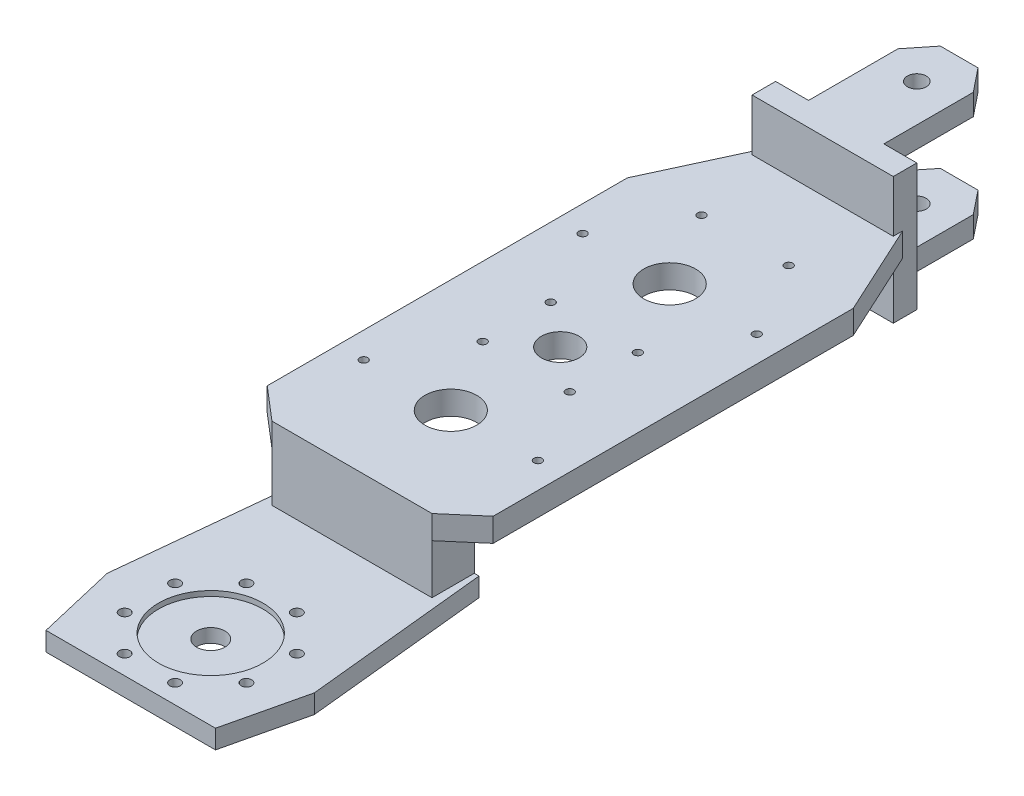
SolidWorks part; units mm, degrees
ref_plane "Front Plane" through (0, 0, 0) normal (0, 0, 1) x (1, 0, 0)
ref_plane "Top Plane" through (0, 0, 0) normal (0, 1, 0) x (1, 0, 0)
ref_plane "Right Plane" through (0, 0, 0) normal (1, 0, 0) x (0, 0, -1)
ref_plane "PL_Knee_Plate_base" through (0, -34, 0) normal (0, 1, 0) x (1, 0, 0)
sketch "SK_Knee_Plate" plane through (0, -34, 0) normal (0, 1, 0) x (1, 0, 0)
  line L0 (-36, -34) -> (36, -34)
  line L1 (36, -34) -> (44, 0)
  line L2 (44, 0) -> (36, 78)
  line L3 (36, 78) -> (-36, 78)
  line L4 (-36, 78) -> (-44, 0)
  line L5 (-44, 0) -> (-36, -34)
  circle A0 centre (25.8686, 10.7151) radius 2.25
  circle A1 centre (10.7151, 25.8686) radius 2.25
  circle A2 centre (-10.7151, 25.8686) radius 2.25
  circle A3 centre (-25.8686, 10.7151) radius 2.25
  circle A4 centre (-25.8686, -10.7151) radius 2.25
  circle A5 centre (-10.7151, -25.8686) radius 2.25
  circle A6 centre (10.7151, -25.8686) radius 2.25
  circle A7 centre (25.8686, -10.7151) radius 2.25
  circle A8 centre (0, 0) radius 6
  dimension "D11_SK_Knee_Plate" = 4.5
  dimension "D14_SK_Knee_Plate" = 4.5
  dimension "D17_SK_Knee_Plate" = 4.5
  dimension "D20_SK_Knee_Plate" = 4.5
  dimension "D23_SK_Knee_Plate" = 4.5
  dimension "D26_SK_Knee_Plate" = 4.5
  dimension "D29_SK_Knee_Plate" = 4.5
  dimension "D32_SK_Knee_Plate" = 4.5
  dimension "D35_SK_Knee_Plate" = 12
  dimension "P1" = 36
  dimension "P2" = 34
  dimension "P3" = 36
  dimension "P4" = 34
  dimension "P5" = 44
  dimension "P6" = 36
  dimension "P7" = 78
  dimension "P8" = 36
  dimension "P9" = 78
  dimension "P10" = 44
  dimension "P12" = 25.8686
  dimension "P13" = 10.7151
  dimension "P15" = 10.7151
  dimension "P16" = 25.8686
  dimension "P18" = 10.7151
  dimension "P19" = 25.8686
  dimension "P21" = 25.8686
  dimension "P22" = 10.7151
  dimension "P24" = 25.8686
  dimension "P25" = 10.7151
  dimension "P27" = 10.7151
  dimension "P28" = 25.8686
  dimension "P30" = 10.7151
  dimension "P31" = 25.8686
  dimension "P33" = 25.8686
  dimension "P34" = 10.7151
extrude "Knee_Plate" add sketch "SK_Knee_Plate" along normal blind 8
ref_plane "PL_Knee_Pilot_Recess_base" through (0, -26, 0) normal (0, 1, 0) x (1, 0, 0)
sketch "SK_Knee_Pilot_Recess" plane through (0, -26, 0) normal (0, 1, 0) x (1, 0, 0)
  circle A0 centre (0, 0) radius 22.15
  dimension "D1_SK_Knee_Pilot_Recess" = 44.3
extrude "Knee_Pilot_Recess" cut sketch "SK_Knee_Pilot_Recess" against normal blind 2.2
ref_plane "PL_Joggle_base" through (0, 0, -78) normal (0, 0, 1) x (1, 0, 0)
sketch "SK_Joggle" plane through (0, 0, -78) normal (0, 0, 1) x (1, 0, 0)
  line L0 (-34, -34) -> (34, -34)
  line L1 (34, -34) -> (34, 5)
  line L2 (34, 5) -> (-34, 5)
  line L3 (-34, 5) -> (-34, -34)
  dimension "P1" = 34
  dimension "P2" = 34
  dimension "P3" = 34
  dimension "P4" = 34
  dimension "P5" = 34
  dimension "P6" = 5
  dimension "P7" = 34
  dimension "P8" = 5
extrude "Joggle" add sketch "SK_Joggle" along normal blind 18
ref_plane "PL_Web_base" through (0, -5, 0) normal (0, 1, 0) x (1, 0, 0)
sketch "SK_Web" plane through (0, -5, 0) normal (0, 1, 0) x (1, 0, 0)
  line L0 (-34, 60) -> (34, 60)
  line L1 (34, 60) -> (48, 72)
  line L2 (48, 72) -> (48, 225)
  line L3 (48, 225) -> (30, 264)
  line L4 (30, 264) -> (-30, 264)
  line L5 (-30, 264) -> (-48, 225)
  line L6 (-48, 225) -> (-48, 72)
  line L7 (-48, 72) -> (-34, 60)
  circle A0 centre (37, 102) radius 1.7
  circle A1 centre (18.5, 134.0429) radius 1.7
  circle A2 centre (-18.5, 134.0429) radius 1.7
  circle A3 centre (-37, 102) radius 1.7
  circle A4 centre (-18.5, 69.9571) radius 1.7
  circle A5 centre (18.5, 69.9571) radius 1.7
  circle A6 centre (37, 195) radius 1.7
  circle A7 centre (18.5, 227.0429) radius 1.7
  circle A8 centre (-18.5, 227.0429) radius 1.7
  circle A9 centre (-37, 195) radius 1.7
  circle A10 centre (-18.5, 162.9571) radius 1.7
  circle A11 centre (18.5, 162.9571) radius 1.7
  circle A12 centre (0, 102) radius 11
  circle A13 centre (0, 195) radius 11
  circle A14 centre (0, 148.5) radius 8
  dimension "D17_SK_Web" = 3.4
  dimension "D20_SK_Web" = 3.4
  dimension "D23_SK_Web" = 3.4
  dimension "D26_SK_Web" = 3.4
  dimension "D29_SK_Web" = 3.4
  dimension "D32_SK_Web" = 3.4
  dimension "D35_SK_Web" = 3.4
  dimension "D38_SK_Web" = 3.4
  dimension "D41_SK_Web" = 3.4
  dimension "D44_SK_Web" = 3.4
  dimension "D47_SK_Web" = 3.4
  dimension "D50_SK_Web" = 3.4
  dimension "D53_SK_Web" = 22
  dimension "D55_SK_Web" = 22
  dimension "D57_SK_Web" = 16
  dimension "P1" = 34
  dimension "P2" = 60
  dimension "P3" = 34
  dimension "P4" = 60
  dimension "P5" = 48
  dimension "P6" = 72
  dimension "P7" = 48
  dimension "P8" = 225
  dimension "P9" = 30
  dimension "P10" = 264
  dimension "P11" = 30
  dimension "P12" = 264
  dimension "P13" = 48
  dimension "P14" = 225
  dimension "P15" = 48
  dimension "P16" = 72
  dimension "P18" = 37
  dimension "P19" = 102
  dimension "P21" = 18.5
  dimension "P22" = 134.0429
  dimension "P24" = 18.5
  dimension "P25" = 134.0429
  dimension "P27" = 37
  dimension "P28" = 102
  dimension "P30" = 18.5
  dimension "P31" = 69.9571
  dimension "P33" = 18.5
  dimension "P34" = 69.9571
  dimension "P36" = 37
  dimension "P37" = 195
  dimension "P39" = 18.5
  dimension "P40" = 227.0429
  dimension "P42" = 18.5
  dimension "P43" = 227.0429
  dimension "P45" = 37
  dimension "P46" = 195
  dimension "P48" = 18.5
  dimension "P49" = 162.9571
  dimension "P51" = 18.5
  dimension "P52" = 162.9571
  dimension "P54" = 102
  dimension "P56" = 195
  dimension "P58" = 148.5
extrude "Web" add sketch "SK_Web" along normal blind 10
ref_plane "PL_Fork_Bar_base" through (0, 0, -270) normal (0, 0, 1) x (1, 0, 0)
sketch "SK_Fork_Bar" plane through (0, 0, -270) normal (0, 0, 1) x (1, 0, 0)
  line L0 (-30, -27) -> (30, -27)
  line L1 (30, -27) -> (30, 27)
  line L2 (30, 27) -> (-30, 27)
  line L3 (-30, 27) -> (-30, -27)
  dimension "P1" = 30
  dimension "P2" = 27
  dimension "P3" = 30
  dimension "P4" = 27
  dimension "P5" = 30
  dimension "P6" = 27
  dimension "P7" = 30
  dimension "P8" = 27
extrude "Fork_Bar" add sketch "SK_Fork_Bar" along normal blind 10
ref_plane "PL_Tine_Lat_base" through (0, 18, 0) normal (0, 1, 0) x (1, 0, 0)
sketch "SK_Tine_Lat" plane through (0, 18, 0) normal (0, 1, 0) x (1, 0, 0)
  line L0 (-16, 260) -> (16, 260)
  line L1 (16, 260) -> (16, 308)
  line L2 (16, 308) -> (8, 318)
  line L3 (8, 318) -> (-8, 318)
  line L4 (-8, 318) -> (-16, 308)
  line L5 (-16, 308) -> (-16, 260)
  circle A0 centre (0, 300) radius 4
  dimension "D13_SK_Tine_Lat" = 8
  dimension "P1" = 16
  dimension "P2" = 260
  dimension "P3" = 16
  dimension "P4" = 260
  dimension "P5" = 16
  dimension "P6" = 308
  dimension "P7" = 8
  dimension "P8" = 318
  dimension "P9" = 8
  dimension "P10" = 318
  dimension "P11" = 16
  dimension "P12" = 308
  dimension "P14" = 300
extrude "Tine_Lat" add sketch "SK_Tine_Lat" along normal blind 9
ref_plane "PL_Tine_Med_base" through (0, -27, 0) normal (0, 1, 0) x (1, 0, 0)
sketch "SK_Tine_Med" plane through (0, -27, 0) normal (0, 1, 0) x (1, 0, 0)
  line L0 (-16, 260) -> (16, 260)
  line L1 (16, 260) -> (16, 308)
  line L2 (16, 308) -> (8, 318)
  line L3 (8, 318) -> (-8, 318)
  line L4 (-8, 318) -> (-16, 308)
  line L5 (-16, 308) -> (-16, 260)
  circle A0 centre (0, 300) radius 4
  dimension "D13_SK_Tine_Med" = 8
  dimension "P1" = 16
  dimension "P2" = 260
  dimension "P3" = 16
  dimension "P4" = 260
  dimension "P5" = 16
  dimension "P6" = 308
  dimension "P7" = 8
  dimension "P8" = 318
  dimension "P9" = 8
  dimension "P10" = 318
  dimension "P11" = 16
  dimension "P12" = 308
  dimension "P14" = 300
extrude "Tine_Med" add sketch "SK_Tine_Med" along normal blind 9
equation "\"Shin_length\" = 300"
equation "\"AnkleA_z\" = -102"
equation "\"AnkleB_z\" = -195"
